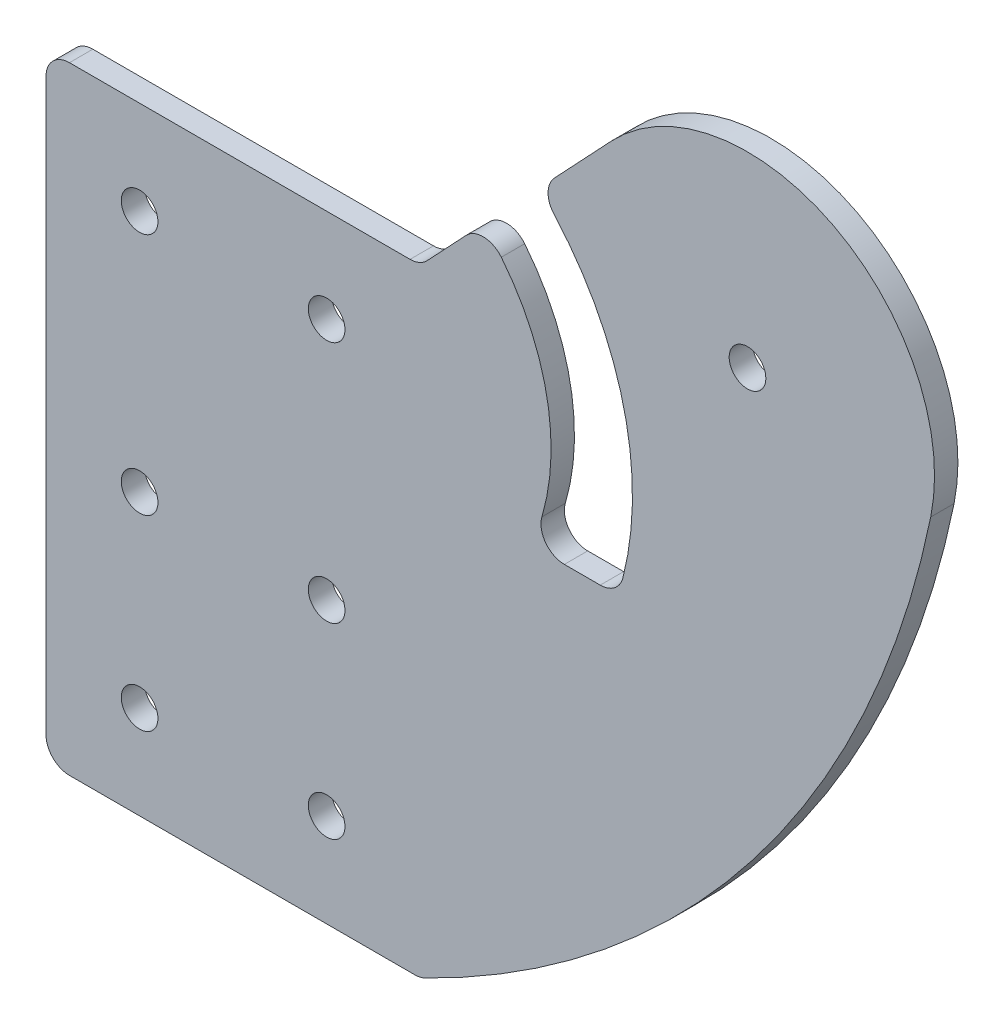
SolidWorks part; units mm, degrees
material "6061-T6 (SS)"
ref_plane "Front Plane" through (0, 0, 0) normal (0, 0, 1) x (1, 0, 0)
ref_plane "Top Plane" through (0, 0, 0) normal (0, 1, 0) x (1, 0, 0)
ref_plane "Right Plane" through (0, 0, 0) normal (1, 0, 0) x (0, 0, -1)
sketch "Sketch2" plane through (0, 0, 0) normal (0, 0, 1) x (1, 0, 0)
  line L0 (50.8, 83.82) -> (59.1187, 92.6561)
  line L1 (0, 0) -> (50.8, 0)
  line L2 (0, 0) -> (0, 83.82)
  line L3 (0, 83.82) -> (50.8, 83.82)
  line L11 (59.1187, 92.6561) -> (59.384, 92.938)
  line L12 (65.8081, 58.42) -> (77.6394, 58.42)
  line L14 (76.7561, 111.3908) -> (66.9585, 100.9837)
  circle A2 centre (95.25, 93.98) radius 2.4892
  arc A3 (50.8, 0) -> (120.1297, 88.8651) centre (-4.2686, 114.4397) ccw
  circle A4 centre (38.1, 71.12) radius 4.7879 construction
  circle A5 centre (13.208, 97.028) radius 4.7625 construction
  arc A8 (120.1297, 88.8651) -> (76.7561, 111.3908) centre (95.25, 93.98) ccw
  arc A9 (65.8081, 58.42) -> (59.384, 92.938) centre (38.1, 71.12) ccw
  arc A10 (77.6394, 58.42) -> (66.9585, 100.9837) centre (38.1, 71.12) ccw
  dimension "D3" = 50.8
  dimension "D5" = 95.25
  dimension "D4" = 4.9784
  dimension "D7" = 254
  dimension "D11" = 9.5758
  dimension "D8" = 60.96
  dimension "D9" = 83.058
  dimension "D16" = 9.525
  dimension "D1" = 50.8
  dimension "D2" = 83.82
  dimension "D6" = 93.98
  dimension "D10" = 25.4
  dimension "D12" = 38.1
  dimension "D13" = 12.7
  dimension "D14" = 25.908
  dimension "D15" = 24.892
extrude "Boss-Extrude1" add sketch "Sketch2" against normal blind 3.175
sketch "Sketch3" plane through (0, 0, 0) normal (0, 0, 1) x (1, 0, 0)
  line L0 (50.8, 83.82) -> (0, 83.82) construction
  line L1 (0, 83.82) -> (0, 0) construction
  circle A0 centre (12.7, 71.12) radius 2.4892
  circle A17 centre (38.1, 71.12) radius 2.4892
  circle A24 centre (12.7, 38.1) radius 2.4892
  circle A25 centre (12.7, 12.7) radius 2.4892
  circle A26 centre (12.7, -12.7) radius 2.4892
  circle A27 centre (12.7, -38.1) radius 2.4892
  circle A28 centre (12.7, -63.5) radius 2.4892
  circle A33 centre (38.1, 12.7) radius 2.4892
  circle A34 centre (38.1, -12.7) radius 2.4892
  circle A35 centre (38.1, -38.1) radius 2.4892
  circle A36 centre (38.1, -63.5) radius 2.4892
  circle A41 centre (38.1, 38.1) radius 2.4892
  dimension "D1" = 4.9784
  dimension "D6" = 4.9784
  dimension "D5" = 4.9784
  dimension "D2" = 12.7
  dimension "D3" = 12.7
  dimension "D7" = 12.7
  dimension "D8" = 33.02
  dimension "D4" = 1
  dimension "D9" = 5
  dimension "D10" = 2
extrude "Cut-Extrude1" cut sketch "Sketch3" against normal through all
fillet "Fillet1" radius 3.175 8 edges at (0, 0, -1.5875) (50.8, 83.82, -1.5875) (0, 83.82, -1.5875) (50.8, 0, -1.5875) (77.6394, 58.42, -1.5875) (65.8081, 58.42, -1.5875) (59.384, 92.938, -1.5875) (66.9585, 100.9837, -1.5875)
